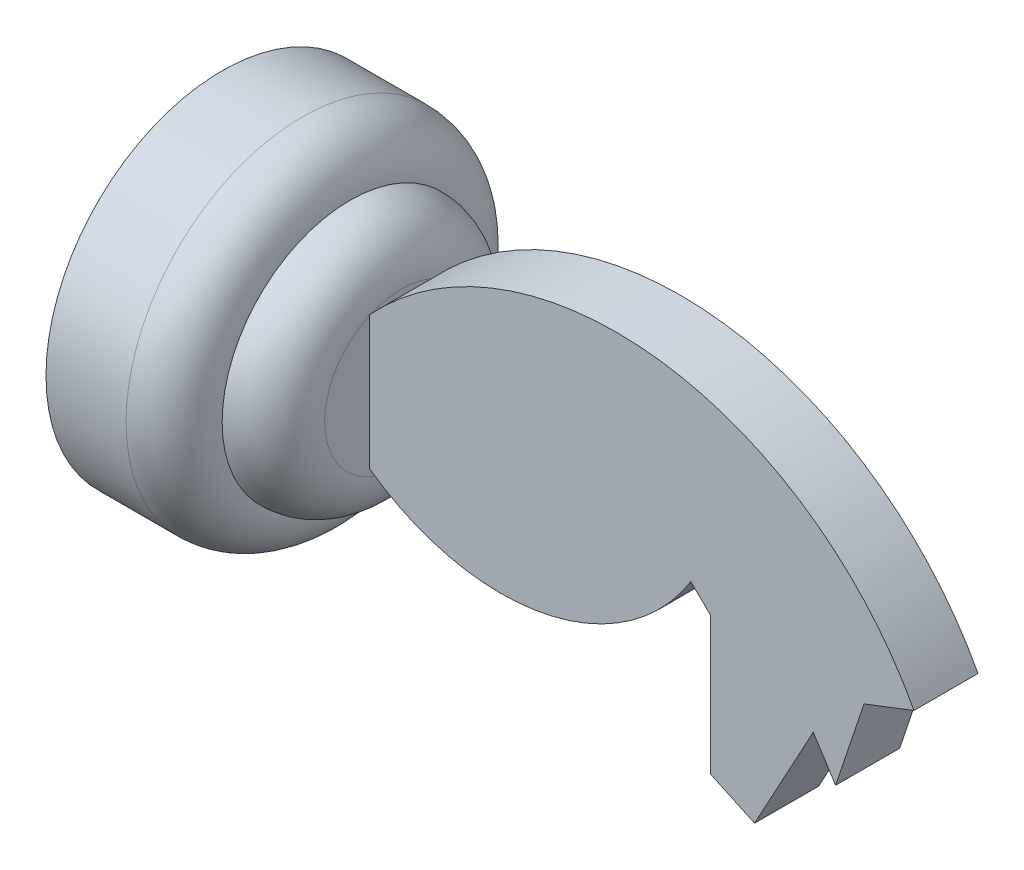
SolidWorks part; units mm, degrees
ref_plane "Спереди" through (0, 0, 0) normal (0, 0, 1) x (1, 0, 0)
ref_plane "Сверху" through (0, 0, 0) normal (0, 1, 0) x (1, 0, 0)
ref_plane "Справа" through (0, 0, 0) normal (1, 0, 0) x (0, 0, -1)
other "Configuration Table"
sketch "Эскиз1" plane through (0, 0, 0) normal (0, 0, 1) x (1, 0, 0)
  line L0 (0, 0) -> (71.2267, 0) construction
sketch "попа" plane through (0, 0, 0) normal (0, 0, 1) x (1, 0, 0)
  line L0 (0, 0) -> (0, 11)
  line L1 (0, 11) -> (5, 11)
  line L3 (0, 0) -> (71.2267, 0) construction
  line L4 (5, 0) -> (0, 0)
  line L7 (11.2, 4.8) -> (11.2, 0)
  line L8 (11.2, 0) -> (0, 0)
  line L9 (8, 0) -> (8, 8)
  line L10 (11.2, 2.4) -> (11.2, 0)
  line L11 (11.2, 4.3) -> (11.2, 0)
  line L12 (11.2, 0) -> (45.2, 0)
  line L16 (1, 0) -> (3.5, 0)
  line L17 (1, 0) -> (1, 5.25)
  line L18 (1, 5.25) -> (3.5, 5.25)
  line L19 (3.5, 5.25) -> (3.5, 0)
  arc A0 (8, 8) -> (5, 11) centre (5, 8) ccw
  arc A1 (11.2, 4.8) -> (8, 8) centre (8, 4.8) ccw
  dimension "D6" = 3
  dimension "D7" = 3.2
  dimension "D9" = 5.25
  dimension "D10" = 2.5
  dimension "D1" = 8
  dimension "D2" = 5
  dimension "D3" = 11.2
  dimension "D4" = 4.8
  dimension "D5" = 8
  dimension "D8" = 1
revolve "Повернуть1" add sketch "попа" angle 360 about L0 region at (4.2267, 5.8894, 0) region at (9.5169, 3.6915, 0)
sketch "вверх" plane through (0, 0, 0) normal (0, 0, 1) x (1, 0, 0)
  line L0 (11.2, 0) -> (11.2, 4.4)
  line L1 (11.2, -4.8) -> (11.2, 4.8) construction
  line L2 (11.2, 0) -> (45.2, 0)
  line L3 (0, 0) -> (71.2267, 0) construction
  line L5 (11.2, 0) -> (11.2, -3.915)
  line L6 (42.083, -1.2) -> (42.083, 0)
  line L7 (40.3075, -6.49) -> (40.3075, 0)
  line L8 (38.912, -4.32) -> (38.912, 0)
  line L9 (31.2635, 0) -> (32.499, -1.1973)
  line L10 (32.499, -1.1973) -> (32.499, -9.7973)
  line L11 (32.499, -9.7973) -> (35.2487, -11.07)
  line L12 (35.2487, -11.07) -> (38.912, -4.32)
  line L13 (38.912, -4.32) -> (40.3075, -6.49)
  line L14 (40.3075, -6.49) -> (42.083, -1.2)
  line L15 (42.083, -1.2) -> (45.2, 0)
  line L16 (35.2487, -11.07) -> (35.2487, 0)
  arc A1 (31.2635, 0) -> (11.2, -3.915) centre (19.3994, 7.4327) cw
  arc A2 (11.2, 4.4) -> (45.2, 0) centre (26.6431, -9.8306) cw
  dimension "D3" = 21
  dimension "D6" = 14
  dimension "D7" = 8.6
  dimension "D1" = 4.4
  dimension "D2" = 34
  dimension "D4" = 20.0635
  dimension "D5" = 3.915
  dimension "D8" = 1.7204
  dimension "D9" = 3.03
  dimension "D10" = 7.68
  dimension "D11" = 2.58
  dimension "D12" = 5.58
  dimension "D13" = 3.34
  dimension "D14" = 13.9365
  dimension "D15" = 1.2
  dimension "D16" = 6.49
  dimension "D17" = 4.32
  dimension "D18" = 11.07
extrude "верх" add sketch "вверх" along normal mid plane 4 contours A2 L0 L2 | A1 L2 L5 | L16 L12 L8 L2 | L11 L16 L2 L9 L10 | L7 L14 L6 L2 | L8 L13 L7 L2 | L6 L15 L2 region at (27.0721, 4.6677, 0) region at (20.1547, -2.7915, 0) region at (33.8562, -5.102, 0) region at (43.122, -0.4, 0) region at (36.8126, -4.0942, 0) region at (40.9917, -2.2258, 0) region at (39.6565, -2.7388, 0)
